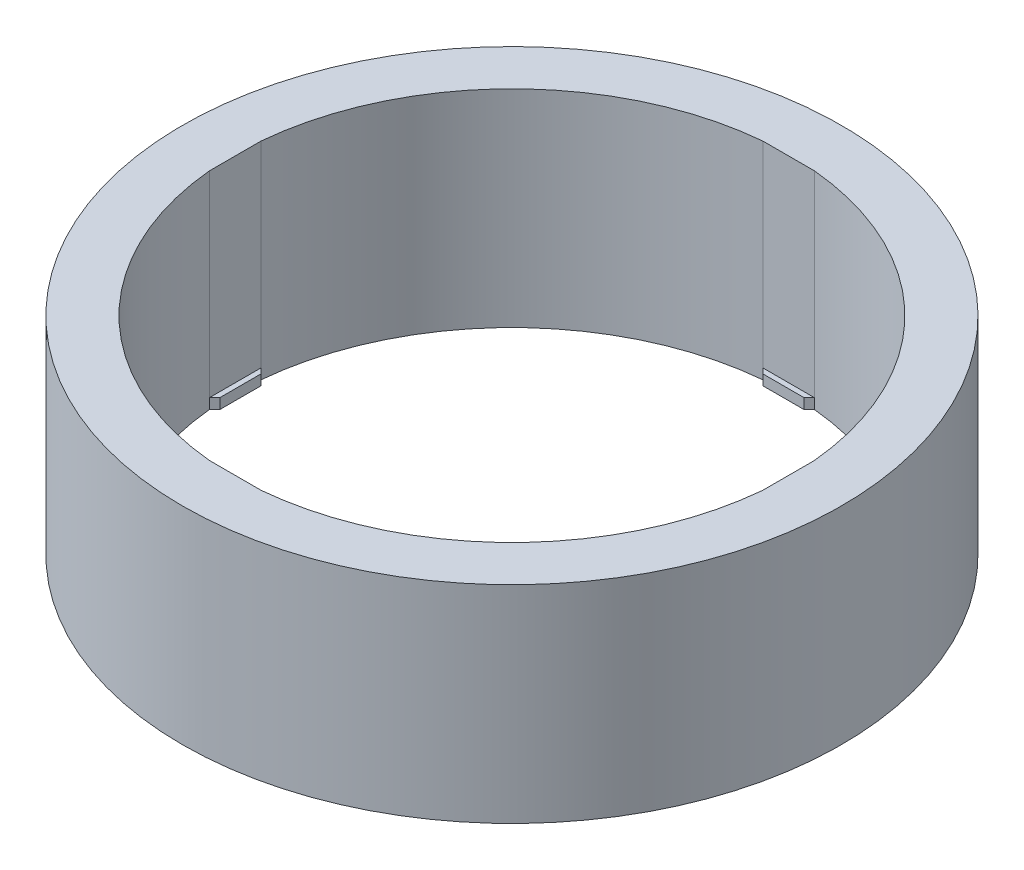
SolidWorks part; units mm, degrees
ref_plane "Front Plane" through (0, 0, 0) normal (0, 0, 1) x (1, 0, 0)
ref_plane "Top Plane" through (0, 0, 0) normal (0, 1, 0) x (1, 0, 0)
ref_plane "Right Plane" through (0, 0, 0) normal (1, 0, 0) x (0, 0, -1)
sketch "Sketch1" plane through (0, 0, 0) normal (0, 1, 0) x (1, 0, 0)
  line L0 (-1, 10.7034) -> (1, 10.7034)
  line L1 (10.7034, 1) -> (10.7034, -1)
  line L2 (1, -10.7034) -> (-1, -10.7034)
  line L3 (-10.7034, -1) -> (-10.7034, 1)
  arc A0 (-1, 10.7034) -> (-10.7034, 1) centre (0, 0) ccw
  circle A1 centre (0, 0) radius 12.75
  arc A2 (10.7034, 1) -> (1, 10.7034) centre (0, 0) ccw
  arc A3 (1, -10.7034) -> (10.7034, -1) centre (0, 0) ccw
  arc A4 (-10.7034, -1) -> (-1, -10.7034) centre (0, 0) ccw
  point P15 (0, 0)
  dimension "D1" = 21.5
  dimension "D2" = 2
  dimension "D3" = 1
  dimension "D4" = 4
extrude "Boss-Extrude1" add sketch "Sketch1" along normal blind 8
sketch "Sketch2" plane through (0, 0, -10.7034) normal (0, 0, 1) x (1, 0, 0)
  line L0 (1, 8) -> (1, 0) construction
  line L1 (-1, 0) -> (1, 0)
  line L2 (-1, 0) -> (-1, 0.4)
  line L3 (-1, 0.4) -> (1, 0.4)
  line L4 (1, 0) -> (1, 0.4)
  dimension "D1" = 0.4
extrude "Boss-Extrude2" add sketch "Sketch2" along normal blind 0.2
sketch "Sketch3" plane through (-10.7034, 0, 0) normal (1, 0, 0) x (0, 0, -1)
  line L0 (1, 8) -> (1, 0) construction
  line L1 (-1, 0) -> (1, 0)
  line L2 (-1, 0) -> (-1, 0.4)
  line L3 (-1, 0.4) -> (1, 0.4)
  line L4 (1, 0) -> (1, 0.4)
  dimension "D1" = 0.4
extrude "Boss-Extrude3" add sketch "Sketch3" along normal blind 0.2
sketch "Sketch4" plane through (0, 0, 10.7034) normal (0, 0, -1) x (-1, 0, 0)
  line L0 (1, 8) -> (1, 0) construction
  line L1 (-1, 0) -> (1, 0)
  line L2 (-1, 0) -> (-1, 0.4)
  line L3 (-1, 0.4) -> (1, 0.4)
  line L4 (1, 0) -> (1, 0.4)
  dimension "D1" = 0.4
extrude "Boss-Extrude4" add sketch "Sketch4" along normal blind 0.2
chamfer "Chamfer1" distance 0.2 angle 45 6 edges at (1, 0.2, -10.5034) (-1, 0.2, -10.5034) (-10.5034, 0.2, 1) (-10.5034, 0.2, -1) (-1, 0.2, 10.5034) (1, 0.2, 10.5034)
sketch "Sketch5" plane through (10.7034, 0, 0) normal (-1, 0, 0) x (0, 0, 1)
  line L0 (1, 8) -> (1, 0) construction
  line L1 (-1, 0) -> (1, 0)
  line L2 (-1, 0) -> (-1, 0.4)
  line L3 (-1, 0.4) -> (1, 0.4)
  line L4 (1, 0) -> (1, 0.4)
  dimension "D1" = 0.4
extrude "Boss-Extrude5" add sketch "Sketch5" along normal blind 0.2
chamfer "Chamfer2" distance 0.2 angle 45 2 edges at (10.5034, 0.2, 1) (10.5034, 0.2, -1)
